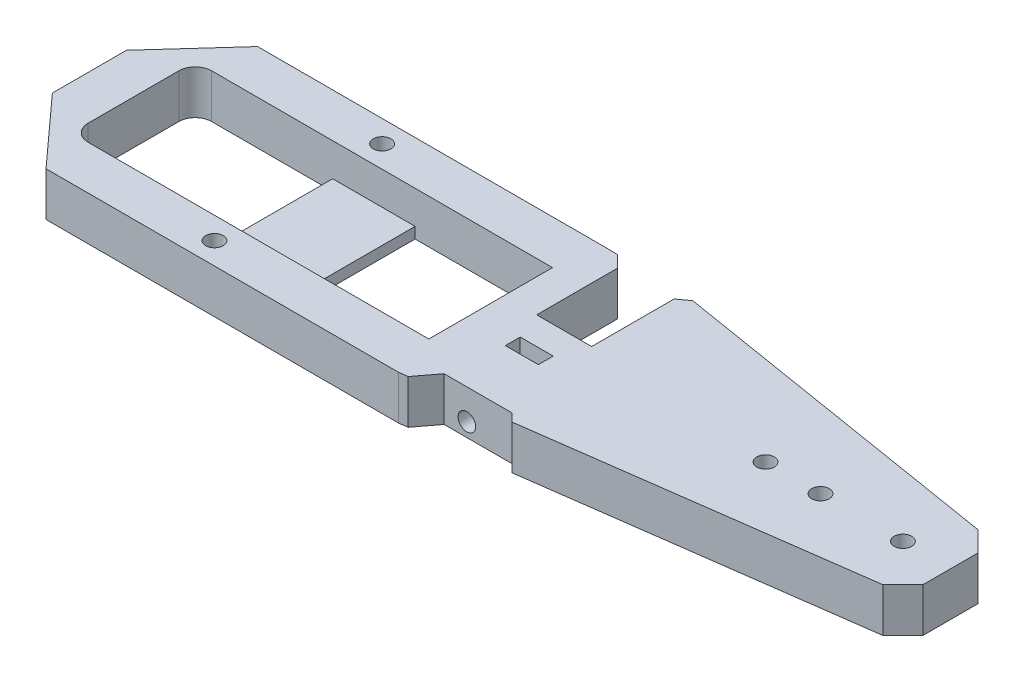
SolidWorks part; units mm, degrees
ref_plane "Front Plane" through (0, 0, 0) normal (0, 0, 1) x (1, 0, 0)
ref_plane "Top Plane" through (0, 0, 0) normal (0, 1, 0) x (1, 0, 0)
ref_plane "Right Plane" through (0, 0, 0) normal (1, 0, 0) x (0, 0, -1)
sketch "Sketch1" plane through (0, 0, 0) normal (0, 1, 0) x (1, 0, 0)
  line L0 (0, 0) -> (-52.2783, 0) construction
  line L1 (-7.5, 7.5) -> (7.5, 7.5) construction
  line L2 (-7.5, 7.5) -> (-7.5, -7.5) construction
  line L3 (-7.5, -7.5) -> (7.5, -7.5) construction
  line L4 (7.5, 7.5) -> (7.5, -7.5) construction
  line L5 (-7.5, 7.5) -> (7.5, -7.5) construction
  line L6 (-7.5, -7.5) -> (7.5, 7.5) construction
  line L7 (-12, 11.25) -> (53, 11.25)
  line L8 (-12, 11.25) -> (-12, -11.25)
  line L9 (-12, -11.25) -> (53, -11.25)
  line L10 (53, 11.25) -> (53, -11.25) construction
  line L11 (0, 0) -> (128, 0) construction
  line L12 (53, 11.25) -> (81, 11.25)
  line L13 (53, 11.25) -> (53, -11.25)
  line L14 (53, -11.25) -> (81, -11.25)
  line L15 (81, 11.25) -> (81, -11.25)
  line L16 (64, 0) -> (64, 19.11)
  line L17 (59, 19.11) -> (59, 2.3703)
  line L18 (59, 2.3703) -> (69, 2.3703)
  line L19 (69, 2.3703) -> (69, 19.11)
  circle A0 centre (64, 19.11) radius 10
  circle A1 centre (64, 19.11) radius 5
  circle A2 centre (0, 0) radius 29.105
  circle A3 centre (0, 0) radius 21.105
  circle A4 centre (113, 0) radius 1.6
  circle A5 centre (103, 0) radius 1.6
  point P0 (0, 0)
  point P14 (64, 0)
  dimension "D9" = 8
  dimension "D10" = 58.21
  dimension "D11" = 15
  dimension "D1" = 15
  dimension "D2" = 15
  dimension "D3" = 22.5
  dimension "D4" = 65
  dimension "D5" = 12
  dimension "D6" = 28
  dimension "D7" = 128
  dimension "D8" = 19.11
  dimension "D12" = 10
  dimension "D13" = 10
sketch "Sketch2" plane through (0, 0, 0) normal (0, 1, 0) x (1, 0, 0)
  line L0 (-12, 11.25) -> (53, 11.25) construction
  line L1 (-12, 11.25) -> (-12, -11.25) construction
  line L2 (-12, -11.25) -> (53, -11.25) construction
  line L3 (-9, 11.25) -> (53, 11.25)
  line L4 (-12, 8.25) -> (-12, -8.25)
  line L5 (-9, -11.25) -> (53, -11.25)
  line L6 (53, 11.25) -> (53, -11.25) construction
  line L7 (53, 11.25) -> (53, -11.25)
  line L8 (128, 0) -> (136.6603, 5) construction
  line L9 (55.5, -19.25) -> (-20, -19.25)
  line L10 (-20, -19.25) -> (-20, 19.25)
  line L11 (-20, 19.25) -> (55.5, 19.25)
  line L12 (69, 2.3703) -> (69, 19.11) construction
  line L13 (136.6603, 5) -> (136.6603, 0)
  line L14 (59, 19.11) -> (59, 2.3703) construction
  line L15 (59, 2.3703) -> (69, 2.3703) construction
  line L16 (59, 2.3703) -> (69, 2.3703)
  line L17 (59, 19.11) -> (59, 2.3703)
  line L18 (69, 2.3703) -> (69, 19.11)
  line L19 (55.5, 19.25) -> (59, 19.11)
  line L20 (0, 0) -> (128, 0) construction
  line L21 (61, -2.6297) -> (67, -2.6297)
  line L22 (61, -2.6297) -> (61, -5.3297)
  line L23 (61, -5.3297) -> (67, -5.3297)
  line L24 (67, -2.6297) -> (67, -5.3297)
  line L25 (61, -2.6297) -> (67, -5.3297) construction
  line L26 (61, -5.3297) -> (67, -2.6297) construction
  line L27 (13, 29.746) -> (23, 29.746) construction
  line L28 (13, 29.746) -> (13, -29.746) construction
  line L29 (13, -29.746) -> (23, -29.746) construction
  line L30 (23, 29.746) -> (23, -29.746) construction
  line L31 (13, 29.746) -> (23, -29.746) construction
  line L32 (13, -29.746) -> (23, 29.746) construction
  line L33 (136.6603, 5) -> (133, 8.6603)
  line L34 (69, 19.11) -> (133, 8.6603)
  line L35 (55.5, -19.25) -> (133, -8.6603)
  line L36 (133, -8.6603) -> (136.6603, -5)
  line L37 (136.6603, -5) -> (136.6603, 0)
  line L38 (-8.6521, 19.25) -> (-20, 6.7395)
  line L40 (-8.6521, -19.25) -> (-20, -6.7395)
  line L41 (61, -18.4985) -> (61, -15.3297)
  line L42 (61, -15.3297) -> (71.8782, -15.3297)
  line L43 (71.8782, -15.3297) -> (71.8782, -17.012)
  circle A0 centre (128, 0) radius 1.6
  arc A1 (128, -10) -> (128, 10) centre (128, 0) ccw construction
  circle A2 centre (18, 15.25) radius 1.6
  circle A3 centre (18, -15.25) radius 1.6
  arc A4 (-9, 11.25) -> (-12, 8.25) centre (-9, 8.25) ccw
  arc A5 (-12, -8.25) -> (-9, -11.25) centre (-9, -8.25) ccw
  circle A6 centre (0, 0) radius 21.105 construction
  point P17 (64, -3.9797)
  point P22 (18, 0)
  dimension "D1" = 10
  dimension "D9" = 30
  dimension "D11" = 4
  dimension "D14" = 3
  dimension "D15" = 3
  dimension "D2" = 8
  dimension "D3" = 8
  dimension "D4" = 8
  dimension "D5" = 2.7
  dimension "D6" = 6
  dimension "D7" = 10
  dimension "D8" = 25
  dimension "D10" = 4
  dimension "D12" = 150
  dimension "D13" = 45
  dimension "D16" = 5
  dimension "D17" = 10
extrude "Boss-Extrude1" add sketch "Sketch2" along normal blind 8 contours L40 L9 L35 L36 L37 L13 L33 L34 L18 L16 L17 L19 L11 L38 L10 A5 L4 A4 L3 L7 L5 A3 A2 A0 L21 L24 L23 L22 region at (64.0786, 0, 0.0818)
sketch "Sketch4" plane through (0, 0, 0) normal (0, -1, 0) x (-1, 0, 0)
  line L0 (0, 0) -> (-128, 0) construction
  line L1 (-13, -19.25) -> (-28, -19.25)
  line L2 (-13, -19.25) -> (-13, 19.25)
  line L3 (-13, 19.25) -> (-28, 19.25)
  line L4 (-28, -19.25) -> (-28, 19.25)
  line L5 (-13, -19.25) -> (-28, 19.25) construction
  line L6 (-13, 19.25) -> (-28, -19.25) construction
  line L8 (12, 11.25) -> (12, -11.25) construction
  line L9 (8.6521, 19.25) -> (-55.5, 19.25) construction
  point P0 (-20.5, 0)
  dimension "D1" = 15
  dimension "D2" = 25
extrude "Boss-Extrude2" add sketch "Sketch4" against normal blind 2
chamfer "Chamfer2" distance 2 angle 45 2 edges at (59, 4, -19.11) (69, 4, -19.11) first distance on face at (59, 4, -10.7401) first distance on face at (101, 4, -13.8851)
sketch "Sketch3" plane through (0, 0, -2.3703) normal (0, 0, -1) x (-1, 0, 0)
  line L0 (-54, 0) -> (-74, 0) construction
  line L1 (-59, 0) -> (-69, 0) construction
  line L2 (-59, 0) -> (-69, 0)
  circle A0 centre (-64, 2.5) radius 1.6
  point P6 (-64, 0)
  dimension "D1" = 3.2
  dimension "D2" = 2.5
extrude "Cut-Extrude1" cut sketch "Sketch3" against normal through all contours A0 region at (64, 2.5, -2.3703)
sketch "Sketch5" plane through (0, 0, 0) normal (0, -1, 0) x (1, 0, 0)
  line L1 (21.0617, 14.0435) -> (20.5758, 17.2983)
  line L2 (20.5758, 17.2983) -> (17.514, 18.5048)
  line L3 (17.514, 18.5048) -> (14.9383, 16.4565)
  line L4 (14.9383, 16.4565) -> (15.4242, 13.2017)
  line L5 (15.4242, 13.2017) -> (18.486, 11.9952)
  line L6 (18.486, 11.9952) -> (21.0617, 14.0435)
  line L7 (21.489, -15.7887) -> (20.211, -12.4978)
  line L8 (20.211, -12.4978) -> (16.722, -11.9591)
  line L9 (16.722, -11.9591) -> (14.511, -14.7113)
  line L10 (14.511, -14.7113) -> (15.789, -18.0022)
  line L11 (15.789, -18.0022) -> (19.278, -18.5409)
  line L12 (19.278, -18.5409) -> (21.489, -15.7887)
  circle A0 centre (18, 15.25) radius 2.85 construction
  circle A1 centre (18, -15.25) radius 3.0574 construction
  dimension "D1" = 5.7
  dimension "D2" = 5.7
extrude "Cut-Extrude2" cut sketch "Sketch5" against normal blind 2.4
ref_axis "Axis1" through (0, 0, 0) along (0, -1, 0)
sketch "Sketch6" plane through (0, 0, 0) normal (0, 0, 1) x (1, 0, 0)
  line L0 (113, 0) -> (113, 3.3)
  line L1 (113, 0) -> (109.7, 0)
  line L2 (0, 0) -> (128, 0) construction
  line L3 (109.7, 0) -> (113, 3.3)
  point P0 (113, 0)
  dimension "D1" = 45
  dimension "D2" = 3.3
revolve "Cut-Revolve1" cut sketch "Sketch6" angle 360 about L0
pattern_linear "LPattern1" count 2 spacing 10 along (-1, 0, 0) of "Cut-Revolve1"
sketch "Sketch7" plane through (0, 0, 0) normal (0, -1, 0) x (1, 0, 0)
  circle A0 centre (113, 0) radius 1.6 construction
  circle A1 centre (113, 0) radius 1.6
  circle A2 centre (103, 0) radius 1.6 construction
  circle A3 centre (103, 0) radius 1.6
extrude "Cut-Extrude3" cut sketch "Sketch7" against normal through all
chamfer "Chamfer4" distance 4 angle 45 1 edges at (61, 4, 18.4985) first distance on face at (58.25, 4, 18.8742)
chamfer "Chamfer5" distance 2 angle 45 1 edges at (71.8782, 4, 17.012) first distance on face at (71.8782, 4, 16.1709)
